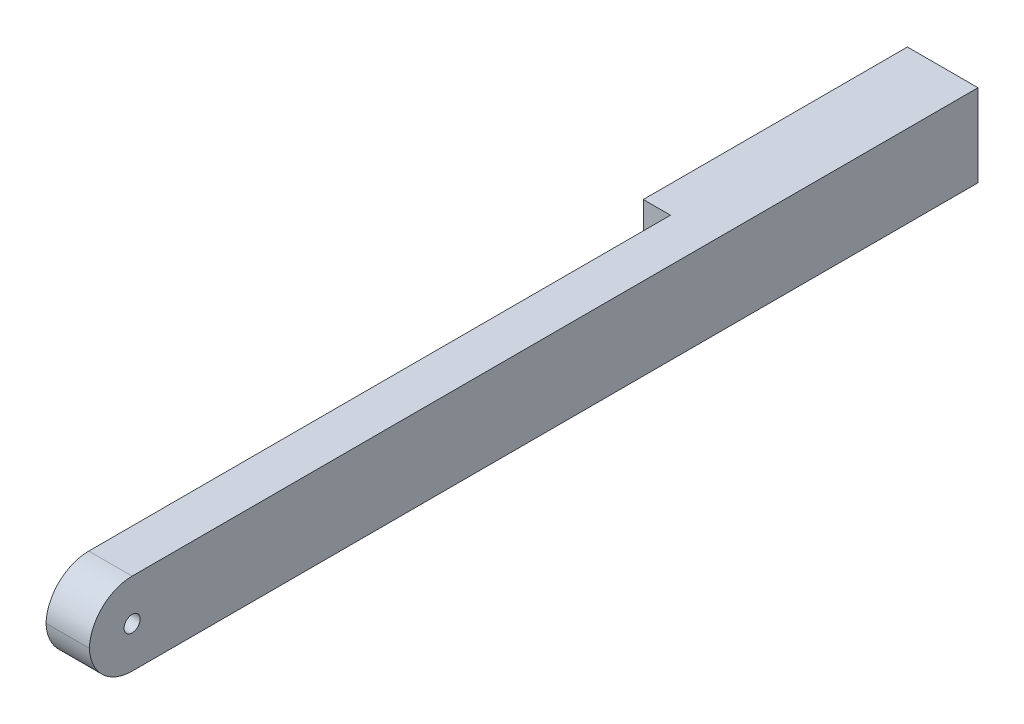
SolidWorks part; units mm, degrees
ref_plane "Ebene vorne" through (0, 0, 0) normal (0, 0, 1) x (1, 0, 0)
ref_plane "Ebene oben" through (0, 0, 0) normal (0, 1, 0) x (1, 0, 0)
ref_plane "Ebene rechts" through (0, 0, 0) normal (1, 0, 0) x (0, 0, -1)
sketch "Skizze1" plane through (0, 0, 0) normal (0, 0, 1) x (1, 0, 0)
  line L1 (-33, -38.5) -> (33, -38.5)
  line L2 (-33, -38.5) -> (-33, 38.5)
  line L3 (-33, 38.5) -> (33, 38.5)
  line L4 (33, -38.5) -> (33, 38.5)
  line L5 (-33, -38.5) -> (33, 38.5) construction
  line L6 (-33, 38.5) -> (33, -38.5) construction
  point P0 (0, 0)
  dimension "D1" = 77
  dimension "D2" = 66
extrude "Aufsatz-Linear austragen1" add sketch "Skizze1" along normal blind 831
sketch "Skizze2" plane through (0, 0, 0) normal (0, 0, -1) x (-1, 0, 0)
  line L0 (33, -20.5) -> (33, 8.5)
  line L1 (33, -20.5) -> (8, -20.5)
  line L2 (33, 8.5) -> (8, 8.5)
  line L3 (8, -20.5) -> (8, 8.5)
  line L4 (33, 38.5) -> (33, -38.5) construction
  line L5 (33, -38.5) -> (-33, -38.5) construction
  dimension "D1" = 18
  dimension "D2" = 25
  dimension "D3" = 29
extrude "Schnitt-Linear austragen1" cut sketch "Skizze2" against normal up to surface (831 mm away) up to face at (0, 0, 831)
sketch "Skizze3" plane through (-8, 0, 0) normal (-1, 0, 0) x (0, 0, 1)
  line L0 (18.367, -20.5) -> (10, -20.5)
  line L1 (0, -20.5) -> (3.0059, -12.2151)
  line L2 (3.0059, -12.2151) -> (5.361, -12.2151)
  line L3 (5.361, -12.2151) -> (8.367, -20.5)
  line L4 (831, -20.5) -> (0, -20.5) construction
  line L5 (8.367, -20.5) -> (0, -20.5)
  line L6 (10, -20.5) -> (13.0059, -12.2151)
  line L7 (13.0059, -12.2151) -> (15.361, -12.2151)
  line L8 (15.361, -12.2151) -> (18.367, -20.5)
  line L9 (28.367, -20.5) -> (20, -20.5)
  line L10 (20, -20.5) -> (23.0059, -12.2151)
  line L11 (23.0059, -12.2151) -> (25.361, -12.2151)
  line L12 (25.361, -12.2151) -> (28.367, -20.5)
  line L13 (38.367, -20.5) -> (30, -20.5)
  line L14 (30, -20.5) -> (33.0059, -12.2151)
  line L15 (33.0059, -12.2151) -> (35.361, -12.2151)
  line L16 (35.361, -12.2151) -> (38.367, -20.5)
  line L17 (48.367, -20.5) -> (40, -20.5)
  line L18 (40, -20.5) -> (43.0059, -12.2151)
  line L19 (43.0059, -12.2151) -> (45.361, -12.2151)
  line L20 (45.361, -12.2151) -> (48.367, -20.5)
  line L21 (58.367, -20.5) -> (50, -20.5)
  line L22 (50, -20.5) -> (53.0059, -12.2151)
  line L23 (53.0059, -12.2151) -> (55.361, -12.2151)
  line L24 (55.361, -12.2151) -> (58.367, -20.5)
  line L25 (68.367, -20.5) -> (60, -20.5)
  line L26 (60, -20.5) -> (63.0059, -12.2151)
  line L27 (63.0059, -12.2151) -> (65.361, -12.2151)
  line L28 (65.361, -12.2151) -> (68.367, -20.5)
  line L29 (78.367, -20.5) -> (70, -20.5)
  line L30 (70, -20.5) -> (73.0059, -12.2151)
  line L31 (73.0059, -12.2151) -> (75.361, -12.2151)
  line L32 (75.361, -12.2151) -> (78.367, -20.5)
  line L33 (88.367, -20.5) -> (80, -20.5)
  line L34 (80, -20.5) -> (83.0059, -12.2151)
  line L35 (83.0059, -12.2151) -> (85.361, -12.2151)
  line L36 (85.361, -12.2151) -> (88.367, -20.5)
  line L37 (98.367, -20.5) -> (90, -20.5)
  line L38 (90, -20.5) -> (93.0059, -12.2151)
  line L39 (93.0059, -12.2151) -> (95.361, -12.2151)
  line L40 (95.361, -12.2151) -> (98.367, -20.5)
  line L41 (108.367, -20.5) -> (100, -20.5)
  line L42 (100, -20.5) -> (103.0059, -12.2151)
  line L43 (103.0059, -12.2151) -> (105.361, -12.2151)
  line L44 (105.361, -12.2151) -> (108.367, -20.5)
  line L45 (118.367, -20.5) -> (110, -20.5)
  line L46 (110, -20.5) -> (113.0059, -12.2151)
  line L47 (113.0059, -12.2151) -> (115.361, -12.2151)
  line L48 (115.361, -12.2151) -> (118.367, -20.5)
  line L49 (128.367, -20.5) -> (120, -20.5)
  line L50 (120, -20.5) -> (123.0059, -12.2151)
  line L51 (123.0059, -12.2151) -> (125.361, -12.2151)
  line L52 (125.361, -12.2151) -> (128.367, -20.5)
  line L53 (138.367, -20.5) -> (130, -20.5)
  line L54 (130, -20.5) -> (133.0059, -12.2151)
  line L55 (133.0059, -12.2151) -> (135.361, -12.2151)
  line L56 (135.361, -12.2151) -> (138.367, -20.5)
  line L57 (148.367, -20.5) -> (140, -20.5)
  line L58 (140, -20.5) -> (143.0059, -12.2151)
  line L59 (143.0059, -12.2151) -> (145.361, -12.2151)
  line L60 (145.361, -12.2151) -> (148.367, -20.5)
  line L61 (158.367, -20.5) -> (150, -20.5)
  line L62 (150, -20.5) -> (153.0059, -12.2151)
  line L63 (153.0059, -12.2151) -> (155.361, -12.2151)
  line L64 (155.361, -12.2151) -> (158.367, -20.5)
  line L65 (168.367, -20.5) -> (160, -20.5)
  line L66 (160, -20.5) -> (163.0059, -12.2151)
  line L67 (163.0059, -12.2151) -> (165.361, -12.2151)
  line L68 (165.361, -12.2151) -> (168.367, -20.5)
  line L69 (178.367, -20.5) -> (170, -20.5)
  line L70 (170, -20.5) -> (173.0059, -12.2151)
  line L71 (173.0059, -12.2151) -> (175.361, -12.2151)
  line L72 (175.361, -12.2151) -> (178.367, -20.5)
  line L73 (188.367, -20.5) -> (180, -20.5)
  line L74 (180, -20.5) -> (183.0059, -12.2151)
  line L75 (183.0059, -12.2151) -> (185.361, -12.2151)
  line L76 (185.361, -12.2151) -> (188.367, -20.5)
  line L77 (198.367, -20.5) -> (190, -20.5)
  line L78 (190, -20.5) -> (193.0059, -12.2151)
  line L79 (193.0059, -12.2151) -> (195.361, -12.2151)
  line L80 (195.361, -12.2151) -> (198.367, -20.5)
  line L81 (208.367, -20.5) -> (200, -20.5)
  line L82 (200, -20.5) -> (203.0059, -12.2151)
  line L83 (203.0059, -12.2151) -> (205.361, -12.2151)
  line L84 (205.361, -12.2151) -> (208.367, -20.5)
  line L85 (218.367, -20.5) -> (210, -20.5)
  line L86 (210, -20.5) -> (213.0059, -12.2151)
  line L87 (213.0059, -12.2151) -> (215.361, -12.2151)
  line L88 (215.361, -12.2151) -> (218.367, -20.5)
  line L89 (228.367, -20.5) -> (220, -20.5)
  line L90 (220, -20.5) -> (223.0059, -12.2151)
  line L91 (223.0059, -12.2151) -> (225.361, -12.2151)
  line L92 (225.361, -12.2151) -> (228.367, -20.5)
  line L93 (238.367, -20.5) -> (230, -20.5)
  line L94 (230, -20.5) -> (233.0059, -12.2151)
  line L95 (233.0059, -12.2151) -> (235.361, -12.2151)
  line L96 (235.361, -12.2151) -> (238.367, -20.5)
  line L97 (248.367, -20.5) -> (240, -20.5)
  line L98 (240, -20.5) -> (243.0059, -12.2151)
  line L99 (243.0059, -12.2151) -> (245.361, -12.2151)
  line L100 (245.361, -12.2151) -> (248.367, -20.5)
  line L101 (258.367, -20.5) -> (250, -20.5)
  line L102 (250, -20.5) -> (253.0059, -12.2151)
  line L103 (253.0059, -12.2151) -> (255.361, -12.2151)
  line L104 (255.361, -12.2151) -> (258.367, -20.5)
  line L105 (268.367, -20.5) -> (260, -20.5)
  line L106 (260, -20.5) -> (263.0059, -12.2151)
  line L107 (263.0059, -12.2151) -> (265.361, -12.2151)
  line L108 (265.361, -12.2151) -> (268.367, -20.5)
  line L109 (278.367, -20.5) -> (270, -20.5)
  line L110 (270, -20.5) -> (273.0059, -12.2151)
  line L111 (273.0059, -12.2151) -> (275.361, -12.2151)
  line L112 (275.361, -12.2151) -> (278.367, -20.5)
  line L113 (288.367, -20.5) -> (280, -20.5)
  line L114 (280, -20.5) -> (283.0059, -12.2151)
  line L115 (283.0059, -12.2151) -> (285.361, -12.2151)
  line L116 (285.361, -12.2151) -> (288.367, -20.5)
  line L117 (298.367, -20.5) -> (290, -20.5)
  line L118 (290, -20.5) -> (293.0059, -12.2151)
  line L119 (293.0059, -12.2151) -> (295.361, -12.2151)
  line L120 (295.361, -12.2151) -> (298.367, -20.5)
  line L121 (308.367, -20.5) -> (300, -20.5)
  line L122 (300, -20.5) -> (303.0059, -12.2151)
  line L123 (303.0059, -12.2151) -> (305.361, -12.2151)
  line L124 (305.361, -12.2151) -> (308.367, -20.5)
  line L125 (318.367, -20.5) -> (310, -20.5)
  line L126 (310, -20.5) -> (313.0059, -12.2151)
  line L127 (313.0059, -12.2151) -> (315.361, -12.2151)
  line L128 (315.361, -12.2151) -> (318.367, -20.5)
  line L129 (328.367, -20.5) -> (320, -20.5)
  line L130 (320, -20.5) -> (323.0059, -12.2151)
  line L131 (323.0059, -12.2151) -> (325.361, -12.2151)
  line L132 (325.361, -12.2151) -> (328.367, -20.5)
  line L133 (338.367, -20.5) -> (330, -20.5)
  line L134 (330, -20.5) -> (333.0059, -12.2151)
  line L135 (333.0059, -12.2151) -> (335.361, -12.2151)
  line L136 (335.361, -12.2151) -> (338.367, -20.5)
  line L137 (348.367, -20.5) -> (340, -20.5)
  line L138 (340, -20.5) -> (343.0059, -12.2151)
  line L139 (343.0059, -12.2151) -> (345.361, -12.2151)
  line L140 (345.361, -12.2151) -> (348.367, -20.5)
  line L141 (358.367, -20.5) -> (350, -20.5)
  line L142 (350, -20.5) -> (353.0059, -12.2151)
  line L143 (353.0059, -12.2151) -> (355.361, -12.2151)
  line L144 (355.361, -12.2151) -> (358.367, -20.5)
  line L145 (368.367, -20.5) -> (360, -20.5)
  line L146 (360, -20.5) -> (363.0059, -12.2151)
  line L147 (363.0059, -12.2151) -> (365.361, -12.2151)
  line L148 (365.361, -12.2151) -> (368.367, -20.5)
  line L149 (378.367, -20.5) -> (370, -20.5)
  line L150 (370, -20.5) -> (373.0059, -12.2151)
  line L151 (373.0059, -12.2151) -> (375.361, -12.2151)
  line L152 (375.361, -12.2151) -> (378.367, -20.5)
  line L153 (388.367, -20.5) -> (380, -20.5)
  line L154 (380, -20.5) -> (383.0059, -12.2151)
  line L155 (383.0059, -12.2151) -> (385.361, -12.2151)
  line L156 (385.361, -12.2151) -> (388.367, -20.5)
  line L157 (398.367, -20.5) -> (390, -20.5)
  line L158 (390, -20.5) -> (393.0059, -12.2151)
  line L159 (393.0059, -12.2151) -> (395.361, -12.2151)
  line L160 (395.361, -12.2151) -> (398.367, -20.5)
  line L161 (408.367, -20.5) -> (400, -20.5)
  line L162 (400, -20.5) -> (403.0059, -12.2151)
  line L163 (403.0059, -12.2151) -> (405.361, -12.2151)
  line L164 (405.361, -12.2151) -> (408.367, -20.5)
  line L165 (418.367, -20.5) -> (410, -20.5)
  line L166 (410, -20.5) -> (413.0059, -12.2151)
  line L167 (413.0059, -12.2151) -> (415.361, -12.2151)
  line L168 (415.361, -12.2151) -> (418.367, -20.5)
  line L169 (428.367, -20.5) -> (420, -20.5)
  line L170 (420, -20.5) -> (423.0059, -12.2151)
  line L171 (423.0059, -12.2151) -> (425.361, -12.2151)
  line L172 (425.361, -12.2151) -> (428.367, -20.5)
  line L249 (8.367, -20.5) -> (18.367, -20.5) construction
  line L250 (438.367, -20.5) -> (430, -20.5) [skipped]
  line L251 (430, -20.5) -> (433.0059, -12.2151) [skipped]
  line L252 (433.0059, -12.2151) -> (435.361, -12.2151) [skipped]
  line L253 (435.361, -12.2151) -> (438.367, -20.5) [skipped]
  line L254 (448.367, -20.5) -> (440, -20.5) [skipped]
  line L255 (440, -20.5) -> (443.0059, -12.2151) [skipped]
  line L256 (443.0059, -12.2151) -> (445.361, -12.2151) [skipped]
  line L257 (445.361, -12.2151) -> (448.367, -20.5) [skipped]
  line L258 (458.367, -20.5) -> (450, -20.5) [skipped]
  line L259 (450, -20.5) -> (453.0059, -12.2151) [skipped]
  line L260 (453.0059, -12.2151) -> (455.361, -12.2151) [skipped]
  line L261 (455.361, -12.2151) -> (458.367, -20.5) [skipped]
  line L262 (468.367, -20.5) -> (460, -20.5) [skipped]
  line L263 (460, -20.5) -> (463.0059, -12.2151) [skipped]
  line L264 (463.0059, -12.2151) -> (465.361, -12.2151) [skipped]
  line L265 (465.361, -12.2151) -> (468.367, -20.5) [skipped]
  line L266 (478.367, -20.5) -> (470, -20.5) [skipped]
  line L267 (470, -20.5) -> (473.0059, -12.2151) [skipped]
  line L268 (473.0059, -12.2151) -> (475.361, -12.2151) [skipped]
  line L269 (475.361, -12.2151) -> (478.367, -20.5) [skipped]
  line L270 (488.367, -20.5) -> (480, -20.5) [skipped]
  line L271 (480, -20.5) -> (483.0059, -12.2151) [skipped]
  line L272 (483.0059, -12.2151) -> (485.361, -12.2151) [skipped]
  line L273 (485.361, -12.2151) -> (488.367, -20.5) [skipped]
  line L274 (498.367, -20.5) -> (490, -20.5) [skipped]
  line L275 (490, -20.5) -> (493.0059, -12.2151) [skipped]
  line L276 (493.0059, -12.2151) -> (495.361, -12.2151) [skipped]
  line L277 (495.361, -12.2151) -> (498.367, -20.5) [skipped]
  line L278 (508.367, -20.5) -> (500, -20.5) [skipped]
  line L279 (500, -20.5) -> (503.0059, -12.2151) [skipped]
  line L280 (503.0059, -12.2151) -> (505.361, -12.2151) [skipped]
  line L281 (505.361, -12.2151) -> (508.367, -20.5) [skipped]
  line L282 (518.367, -20.5) -> (510, -20.5) [skipped]
  line L283 (510, -20.5) -> (513.0059, -12.2151) [skipped]
  line L284 (513.0059, -12.2151) -> (515.361, -12.2151) [skipped]
  line L285 (515.361, -12.2151) -> (518.367, -20.5) [skipped]
  line L286 (528.367, -20.5) -> (520, -20.5) [skipped]
  line L287 (520, -20.5) -> (523.0059, -12.2151) [skipped]
  line L288 (523.0059, -12.2151) -> (525.361, -12.2151) [skipped]
  line L289 (525.361, -12.2151) -> (528.367, -20.5) [skipped]
  line L290 (538.367, -20.5) -> (530, -20.5) [skipped]
  line L291 (530, -20.5) -> (533.0059, -12.2151) [skipped]
  line L292 (533.0059, -12.2151) -> (535.361, -12.2151) [skipped]
  line L293 (535.361, -12.2151) -> (538.367, -20.5) [skipped]
  line L294 (548.367, -20.5) -> (540, -20.5) [skipped]
  line L295 (540, -20.5) -> (543.0059, -12.2151) [skipped]
  line L296 (543.0059, -12.2151) -> (545.361, -12.2151) [skipped]
  line L297 (545.361, -12.2151) -> (548.367, -20.5) [skipped]
  line L298 (558.367, -20.5) -> (550, -20.5) [skipped]
  line L299 (550, -20.5) -> (553.0059, -12.2151) [skipped]
  line L300 (553.0059, -12.2151) -> (555.361, -12.2151) [skipped]
  line L301 (555.361, -12.2151) -> (558.367, -20.5) [skipped]
  line L302 (568.367, -20.5) -> (560, -20.5) [skipped]
  line L303 (560, -20.5) -> (563.0059, -12.2151) [skipped]
  line L304 (563.0059, -12.2151) -> (565.361, -12.2151) [skipped]
  line L305 (565.361, -12.2151) -> (568.367, -20.5) [skipped]
  line L306 (578.367, -20.5) -> (570, -20.5) [skipped]
  line L307 (570, -20.5) -> (573.0059, -12.2151) [skipped]
  line L308 (573.0059, -12.2151) -> (575.361, -12.2151) [skipped]
  line L309 (575.361, -12.2151) -> (578.367, -20.5) [skipped]
  line L310 (588.367, -20.5) -> (580, -20.5) [skipped]
  line L311 (580, -20.5) -> (583.0059, -12.2151) [skipped]
  line L312 (583.0059, -12.2151) -> (585.361, -12.2151) [skipped]
  line L313 (585.361, -12.2151) -> (588.367, -20.5) [skipped]
  line L314 (598.367, -20.5) -> (590, -20.5) [skipped]
  line L315 (590, -20.5) -> (593.0059, -12.2151) [skipped]
  line L316 (593.0059, -12.2151) -> (595.361, -12.2151) [skipped]
  line L317 (595.361, -12.2151) -> (598.367, -20.5) [skipped]
  line L318 (608.367, -20.5) -> (600, -20.5) [skipped]
  line L319 (600, -20.5) -> (603.0059, -12.2151) [skipped]
  line L320 (603.0059, -12.2151) -> (605.361, -12.2151) [skipped]
  line L321 (605.361, -12.2151) -> (608.367, -20.5) [skipped]
  line L322 (618.367, -20.5) -> (610, -20.5) [skipped]
  line L323 (610, -20.5) -> (613.0059, -12.2151) [skipped]
  line L324 (613.0059, -12.2151) -> (615.361, -12.2151) [skipped]
  line L325 (615.361, -12.2151) -> (618.367, -20.5) [skipped]
  dimension "D1" = 10
  dimension "D2" = 62
extrude "Aufsatz-Linear austragen3" add sketch "Skizze3" along normal up to vertex (25 mm away) up to point (-33, -20.5, 0)
sketch "Skizze6" plane through (0, 0, 831) normal (0, 0, 1) x (1, 0, 0)
  line L0 (-33, 38.5) -> (-33, -38.5)
  line L1 (-33, 38.5) -> (-7.5521, 38.5)
  line L2 (-33, -38.5) -> (-7.5521, -38.5)
  line L3 (-7.5521, 38.5) -> (-7.5521, -38.5)
extrude "Schnitt-Linear austragen2" cut sketch "Skizze6" against normal blind 584
sketch "Skizze7" plane through (-7.5521, 0, 0) normal (-1, 0, 0) x (0, 0, 1)
  line L0 (831, -38.5) -> (831, 38.5) construction
  circle A0 centre (791, 0) radius 7.5
  point P4 (831, 0)
  dimension "D1" = 15
  dimension "D2" = 40
extrude "Schnitt-Linear austragen3" cut sketch "Skizze7" against normal up to surface (40.5521 mm away) up to face at (33, 0, 415.5)
fillet "Verrundung1" radius 40 2 edges at (12.7239, -38.5, 831) (12.7239, 38.5, 831)
